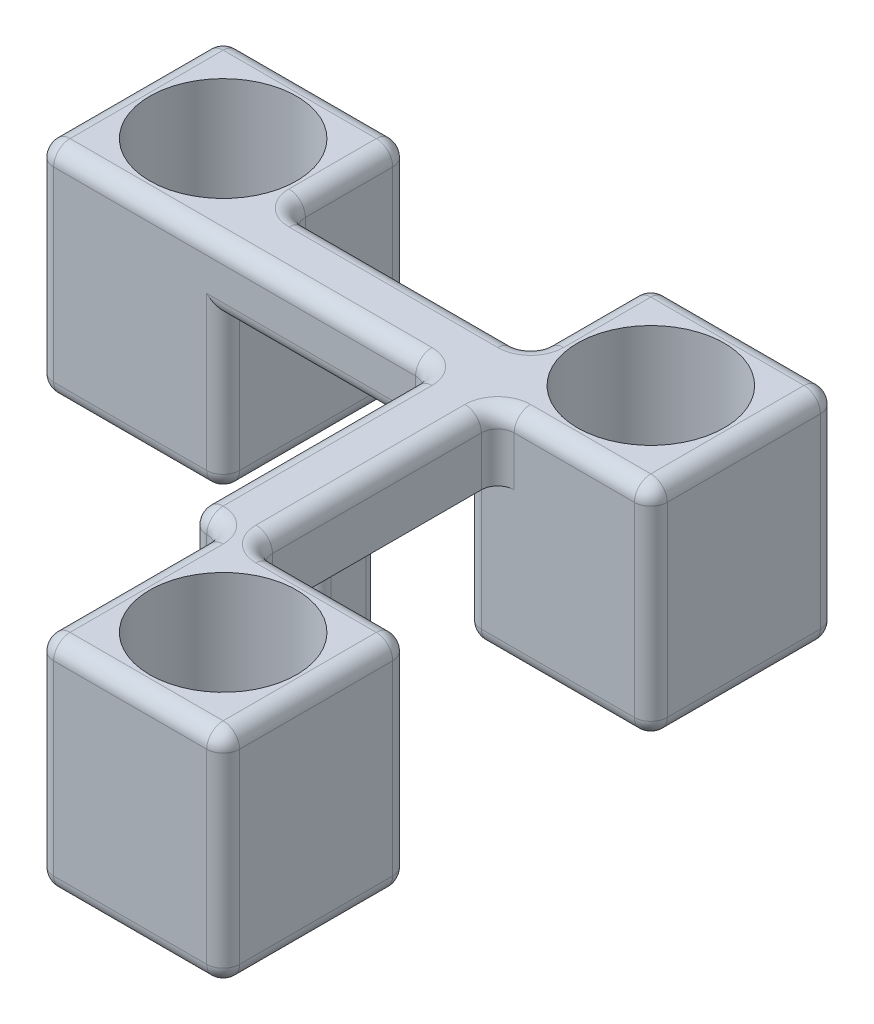
SolidWorks part; units mm, degrees
note: The reader was unsure of these and kept them because the rebuilt part matched: shared geometry of "Sketch1<3>", "Sketch1<4>".
ref_plane "Front Plane" through (0, 0, 0) normal (0, 0, 1) x (1, 0, 0)
ref_plane "Top Plane" through (0, 0, 0) normal (0, 1, 0) x (1, 0, 0)
ref_plane "Right Plane" through (0, 0, 0) normal (1, 0, 0) x (0, 0, -1)
sketch "Sketch1" plane through (0, 0, 0) normal (0, 1, 0) x (1, 0, 0)
  line L0 (-14, 14) -> (14, 14) construction
  line L1 (-14, 14) -> (-14, -14) construction
  line L2 (-14, -14) -> (14, -14) construction
  line L3 (14, 14) -> (14, -14) construction
  line L4 (-14, 14) -> (14, -14) construction
  line L5 (-14, -14) -> (14, 14) construction
  line L6 (4.0147, -0.7154) -> (4.0147, 5.5147)
  line L7 (4.0147, -0.7154) -> (5.1247, -0.7154)
  line L8 (-14, 14) -> (-5.5147, 14)
  line L9 (-14, 14) -> (-14, 5.5147)
  line L10 (-14, 5.5147) -> (-5.5147, 5.5147)
  line L11 (-5.5147, 14) -> (-5.5147, 5.5147)
  line L12 (14, 14) -> (5.5147, 14)
  line L13 (14, 14) -> (14, 5.5147)
  line L14 (14, 5.5147) -> (5.5147, 5.5147)
  line L15 (5.5147, 14) -> (5.5147, 5.5147)
  line L16 (14, -14) -> (5.5147, -14)
  line L17 (14, -14) -> (14, -5.5147)
  line L18 (14, -5.5147) -> (5.5147, -5.5147)
  line L19 (5.5147, -14) -> (5.5147, -5.5147)
  line L20 (4.0147, -0.7154) -> (4.0147, 1.8953)
  line L21 (4.0147, 1.8953) -> (5.1247, 1.8953)
  line L22 (5.1247, -0.7154) -> (5.1247, 1.8953)
  line L23 (4.0147, 5.5147) -> (-5.5147, 5.5147)
  line L24 (-5.5147, 8.5147) -> (5.5147, 8.5147)
  line L25 (4.0147, 1.8953) -> (4.0147, -5.5147)
  line L26 (4.0147, -5.5147) -> (5.5147, -5.5147)
  line L27 (7.0147, 5.5147) -> (7.0147, -5.5147)
  line L28 (-5.5147, 14) -> (-14, 5.5147) construction
  line L29 (-9.7574, 9.7574) -> (9.7574, 9.7574) construction
  line L30 (9.7574, 9.7574) -> (9.7574, -9.7574) construction
  circle A0 centre (-9.7574, 9.7574) radius 3.35
  circle A1 centre (9.7574, 9.7574) radius 3.35
  circle A2 centre (9.7574, -9.7574) radius 3.35
  point P0 (0, 0)
  dimension "D3" = 6.7
  dimension "D1" = 28
  dimension "D2" = 8.4853
  dimension "D4" = 3
  dimension "D5" = 3
  dimension "D6" = 2.6106
  dimension "D7" = 7.41
  dimension "D8" = 1.5
  dimension "D9" = 1.11
extrude "Boss-Extrude1" add sketch "Sketch1" against normal blind 10 contours L11 L8 L9 L10 A0 | L12 L15 L14 L13 A1 | L19 L16 L17 L18 A2
extrude "Boss-Extrude2" add sketch "Sketch1<3>" against normal blind 3 contours L27 L14 L15 L24 L11 L23 L6 L7 L22 L21 L25 L26 L18 | L22 L7 L20 L21
sketch "Sketch1<3>" plane through (0, 0, 0) normal (0, 1, 0) x (1, 0, 0) same geometry as "Sketch1"
extrude "Boss-Extrude3" add sketch "Sketch1<4>" against normal blind 15.67 contours L20 L21 L22 L7
sketch "Sketch1<4>" plane through (0, 0, 0) normal (0, 1, 0) x (1, 0, 0) same geometry as "Sketch1"
fillet "Fillet1" radius 0.75 51 edges at (5.5147, -1.5, 5.5147) (4.0147, -3, 3.115) (4.0147, -3, -3.705) (4.0147, 0, 0) (4.0147, -1.5, -5.5147) (-0.75, -3, -5.5147) (-5.5147, -6.5, -5.5147) (-4.9926, 0, -5.5147) (9.7574, -10, 5.5147) (5.5147, -10, 9.7574) (9.7574, -10, 13.1074) (-9.7574, -10, -5.5147) (-5.5147, -10, -9.7574) (-9.7574, -10, -6.4074) (5.5147, -10, -9.7574) (9.7574, -10, -5.5147) (9.7574, -10, -6.4074) (5.5147, -5, -14) (9.7574, -10, -14) (9.7574, 0, -14) (14, -5, -14) (14, -10, -9.7574) (14, -5, -5.5147) (14, 0, -9.7574) (14, -5, 5.5147) (14, -10, 9.7574) (14, 0, 9.7574) (14, -5, 14) (9.7574, -10, 14) (5.5147, -5, 14) (9.7574, 0, 14) (-9.7574, -10, -14) (-5.5147, -5, -14) (-9.7574, 0, -14) (-14, -5, -5.5147) (-14, -10, -9.7574) (-14, -5, -14) (-14, 0, -9.7574) (-5.5147, -1.5, -8.5147) (4.0147, -1.5, 5.5147) (5.5147, -1.5, -8.5147) (7.0147, -1.5, -5.5147) (7.0147, -1.5, 5.5147) (-5.5147, 0, -11.2574) (5.5147, 0, -11.2574) (10.5074, 0, -5.5147) (10.5074, 0, 5.5147) (5.5147, -6.5, -5.5147) (0, 0, -8.5147) (5.5147, 0, 9.7574) (7.0147, 0, 0)
fillet "Fillet2" radius 0.5 8 edges at (4.0147, -15.67, -0.59) (4.5697, -15.67, -1.8953) (5.1247, -15.67, -0.59) (4.5697, -15.67, 0.7154) (5.1247, -9.335, 0.7154) (4.0147, -8.96, 0.7154) (5.1247, -9.335, -1.8953) (4.0147, -8.96, -1.8953)
ref_plane "Plane1" through (0, -12.17, 0) normal (0, -1, 0) x (-1, 0, 0)
sketch "Sketch3" plane through (0, -12.17, 0) normal (0, -1, 0) x (-1, 0, 0)
  line L0 (-4.5697, -0.2154) -> (-4.5697, 1.3953) construction
  line L1 (-4.6247, -0.2154) -> (-4.5147, -0.2154) construction
  line L2 (-4.5147, 1.3953) -> (-4.6247, 1.3953) construction
  line L3 (-4.0147, 1.3953) -> (-4.0147, -0.2154) construction
  line L4 (-5.6247, -1.2154) -> (-3.5147, -1.2154)
  line L5 (-5.6247, -1.2154) -> (-5.6247, 2.3953)
  line L6 (-5.6247, 2.3953) -> (-3.5147, 2.3953)
  line L7 (-3.5147, -1.2154) -> (-3.5147, 2.3953)
  line L8 (-5.6247, -1.2154) -> (-3.5147, 2.3953) construction
  line L9 (-5.6247, 2.3953) -> (-3.5147, -1.2154) construction
  line L10 (-4.6247, -0.7154) -> (-4.5147, -0.7154) construction
  point P6 (-4.5697, 0.59)
  dimension "D1" = 0.5
  dimension "D2" = 0.5
extrude "Boss-Extrude4" add sketch "Sketch3" against normal blind 0.5
fillet "Fillet3" radius 0.75 4 edges at (3.5147, -11.92, 1.2154) (3.5147, -11.92, -2.3953) (5.6247, -11.92, -2.3953) (5.6247, -11.92, 1.2154)
